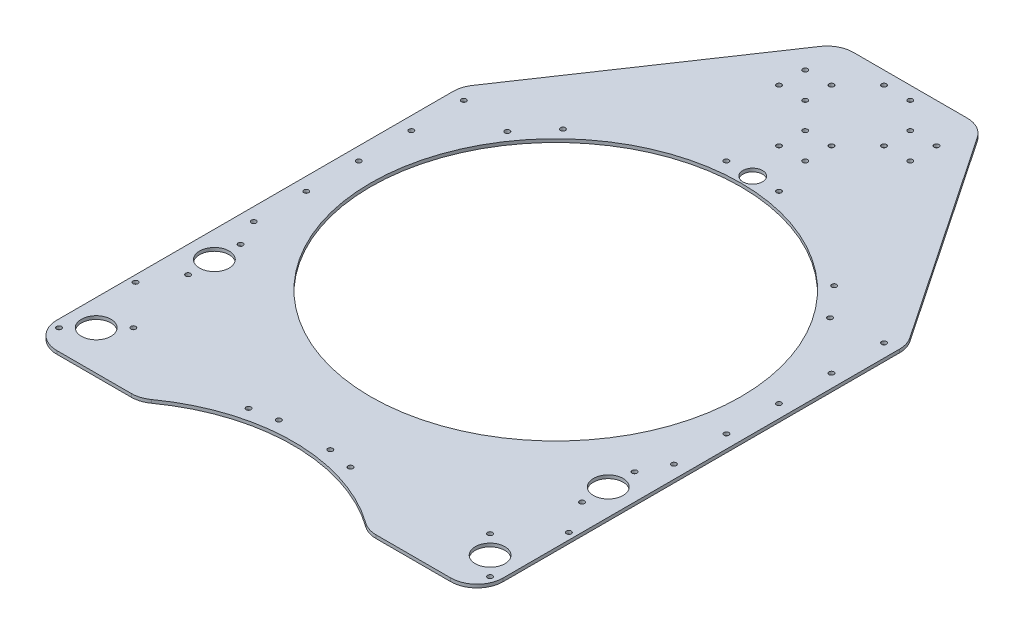
SolidWorks part; units mm, degrees
material "Thornel Mat VMA"
ref_plane "Front Plane" through (0, 0, 0) normal (0, 0, 1) x (1, 0, 0)
ref_plane "Top Plane" through (0, 0, 0) normal (0, 1, 0) x (1, 0, 0)
ref_plane "Right Plane" through (0, 0, 0) normal (1, 0, 0) x (0, 0, -1)
sketch "Sketch1" plane through (0, 0, 0) normal (0, 1, 0) x (1, 0, 0)
  line L1 (-215.9, 342.9) -> (215.9, 342.9)
  line L2 (-215.9, 342.9) -> (-215.9, -342.9)
  line L3 (-215.9, -342.9) -> (215.9, -342.9)
  line L4 (215.9, 342.9) -> (215.9, -342.9)
  line L5 (-215.9, 342.9) -> (215.9, -342.9) construction
  line L6 (-215.9, -342.9) -> (215.9, 342.9) construction
  point P0 (0, 0)
  dimension "D1" = 431.8
  dimension "D2" = 685.8
extrude "Boss-Extrude1" add sketch "Sketch1" along normal blind 3.175
sketch "Sketch2" plane through (0, 3.175, 0) normal (0, 1, 0) x (1, 0, 0)
  line L0 (0, -342.9) -> (0, 342.9) construction
  line L1 (-215.9, -342.9) -> (215.9, -342.9) construction
  line L2 (215.9, 342.9) -> (-215.9, 342.9) construction
  line L3 (-215.9, 342.9) -> (-215.9, -342.9) construction
  line L4 (-208.4605, -322.7605) -> (-190.5, -304.8) construction
  line L5 (-193.1461, -304.8) -> (-215.9, -304.8) construction
  circle A0 centre (-190.5, -304.8) radius 14.3129
  circle A1 centre (-190.5, -190.5) radius 14.3129
  circle A3 centre (190.5, -190.5) radius 14.3129
  circle A4 centre (190.5, -190.5) radius 25.4 construction
  circle A5 centre (-190.5, -190.5) radius 25.4 construction
  circle A6 centre (190.5, -215.9) radius 2.3813
  circle A7 centre (190.5, -165.1) radius 2.3813
  circle A8 centre (-190.5, -215.9) radius 2.3813
  circle A9 centre (-190.5, -165.1) radius 2.3813
  circle A10 centre (-190.5, -304.8) radius 25.4 construction
  circle A11 centre (-208.4605, -322.7605) radius 2.3813
  circle A15 centre (-172.5395, -286.8395) radius 2.3813
  circle A16 centre (172.5395, -286.8395) radius 2.3813
  circle A17 centre (208.4605, -322.7605) radius 2.3813
  circle A18 centre (190.5, -304.8) radius 14.3129
  point P33 (-190.5, -304.8)
  point P34 (-190.5, -304.8)
  dimension "D1" = 28.6258
  dimension "D2" = 28.6258
  dimension "D6" = 50.8
  dimension "D7" = 50.8
  dimension "D8" = 4.7625
  dimension "D9" = 4.7625
  dimension "D10" = 4.7625
  dimension "D11" = 4.7625
  dimension "D12" = 50.8
  dimension "D13" = 4.7625
  dimension "D3" = 38.1
  dimension "D4" = 114.3
  dimension "D5" = 25.4
  dimension "D15" = 45
  dimension "D14" = 2
extrude "Cut-Extrude1" cut sketch "Sketch2" against normal through all
sketch "Sketch3" plane through (0, 0, 0) normal (0, -1, 0) x (-1, 0, 0)
  line L1 (29.8706, 270.2084) -> (-24.7394, 270.2084)
  line L2 (29.8706, 270.2084) -> (29.8706, 216.2334)
  line L3 (29.8706, 216.2334) -> (-24.7394, 216.2334)
  line L4 (-24.7394, 270.2084) -> (-24.7394, 216.2334)
  line L5 (29.8706, 270.2084) -> (-24.7394, 216.2334) construction
  line L6 (29.8706, 216.2334) -> (-24.7394, 270.2084) construction
  point P0 (2.5656, 243.2209)
  dimension "D1" = 53.975
  dimension "D2" = 54.61
extrude "Boss-Extrude2" [suppressed] add sketch "Sketch3" along normal blind 203.2
fillet "Fillet1" [suppressed] radius 20.32
sketch "Sketch4" [suppressed] plane through (0, -203.2, 0) normal (0, -1, 0) x (-1, 0, 0)
  line L0 (-24.7394, 216.2334) -> (29.8706, 216.2334) construction
  line L1 (26.6956, 267.0334) -> (-21.5644, 267.0334)
  line L2 (26.6956, 267.0334) -> (26.6956, 219.4084)
  line L3 (26.6956, 219.4084) -> (-21.5644, 219.4084)
  line L4 (-21.5644, 267.0334) -> (-21.5644, 219.4084)
  line L5 (26.6956, 267.0334) -> (-21.5644, 219.4084) construction
  line L6 (26.6956, 219.4084) -> (-21.5644, 267.0334) construction
  line L7 (29.8706, 270.2084) -> (-24.7394, 270.2084) construction
  line L8 (29.8706, 216.2334) -> (29.8706, 270.2084) construction
  line L9 (-24.7394, 270.2084) -> (-24.7394, 216.2334) construction
  point P0 (2.5656, 243.2209)
  dimension "D1" = 3.175
  dimension "D2" = 3.175
  dimension "D3" = 3.175
  dimension "D4" = 3.175
extrude "Cut-Extrude2" [suppressed] cut sketch "Sketch4" against normal blind 203.2
sketch "Sketch5" [suppressed] plane through (-29.8706, 0, 0) normal (-1, 0, 0) x (0, 0, 1)
  line L0 (-216.2334, -203.2) -> (-216.2334, 0) construction
  line L1 (-216.2334, -203.2) -> (-270.2084, -203.2) construction
  circle A0 centre (-243.2209, -184.15) radius 14.2875
  dimension "D1" = 28.575
  dimension "D2" = 26.9875
  dimension "D3" = 19.05
extrude "Cut-Extrude3" [suppressed] cut sketch "Sketch5" against normal blind 203.2
sketch "Sketch6" plane through (0, 3.175, 0) normal (0, 1, 0) x (1, 0, 0)
  circle A0 centre (0, -50.8) radius 179.07
  dimension "D1" = 358.14
  dimension "D2" = 50.8
extrude "Cut-Extrude4" cut sketch "Sketch6" against normal through all
sketch "Sketch8" plane through (0, 3.175, 0) normal (0, 1, 0) x (1, 0, 0)
  circle A0 centre (0, 139.7) radius 9.525
  circle A2 centre (0, 139.7) radius 25.4 construction
  circle A3 centre (25.4, 139.7) radius 2.3813
  circle A4 centre (-25.4, 139.7) radius 2.3813
  dimension "D1" = 19.05
  dimension "D3" = 50.8
  dimension "D4" = 4.7625
  dimension "D5" = 4.7625
  dimension "D2" = 139.7
extrude "Cut-Extrude6" cut sketch "Sketch8" against normal through all
fillet "Fillet2" radius 25.4 2 edges at (215.9, 1.5875, 342.9) (-215.9, 1.5875, 342.9)
sketch "Sketch10" plane through (0, 3.175, 0) normal (0, 1, 0) x (1, 0, 0)
  line L0 (-215.9, 342.9) -> (-215.9, -317.5) construction
  line L1 (215.9, -317.5) -> (215.9, 342.9) construction
  circle A0 centre (-190.5, 215.9) radius 14.3129
  circle A1 centre (190.5, 215.9) radius 14.3129
  circle A2 centre (-190.5, 215.9) radius 25.4 construction
  circle A3 centre (190.5, 215.9) radius 25.4 construction
  circle A4 centre (190.5, 190.5) radius 2.3813
  circle A5 centre (190.5, 241.3) radius 2.3813
  circle A6 centre (-190.5, 190.5) radius 2.3813
  circle A7 centre (-190.5, 241.3) radius 2.3813
  circle A8 centre (190.5, -190.5) radius 14.3129 construction
  circle A9 centre (-190.5, -190.5) radius 14.3129 construction
  dimension "D1" = 28.6258
  dimension "D2" = 50.8
  dimension "D3" = 28.6258
  dimension "D4" = 50.8
  dimension "D5" = 4.7625
  dimension "D6" = 4.7625
  dimension "D7" = 4.7625
  dimension "D8" = 4.7625
  dimension "D9" = 25.4
  dimension "D10" = 25.4
  dimension "D11" = 406.4
  dimension "D12" = 406.4
extrude "Cut-Extrude8" [suppressed] cut sketch "Sketch10" against normal through all
sketch "Sketch11" plane through (0, 3.175, 0) normal (0, 1, 0) x (1, 0, 0)
  line L0 (0, -50.8) -> (156.0485, 58.4663) construction
  line L6 (0, 0) -> (0, 139.7) construction
  circle A0 centre (0, -50.8) radius 179.07
  circle A1 centre (0, -50.8) radius 179.07 construction
  circle A2 centre (0, -50.8) radius 184.15
  circle A3 centre (0, -50.8) radius 215.9
  circle A4 centre (156.0485, 58.4663) radius 2.3813
  circle A5 centre (131.1838, 87.3342) radius 2.3813
  circle A6 centre (0, -50.8) radius 190.5 construction
  circle A7 centre (-131.1838, 87.3342) radius 2.3813
  circle A8 centre (-156.0485, 58.4663) radius 2.3813
  dimension "D1" = 368.3
  dimension "D6" = 431.8
  dimension "D7" = 381
  dimension "D9" = 4.7625
  dimension "D10" = 4.7625
  dimension "D2" = 55
  dimension "D8" = 38.1
extrude "Cut-Extrude9" cut sketch "Sketch11" against normal through all contours A4 | A5 | A7 | A8 region at (156.0485, 3.175, -58.4663) region at (131.1838, 3.175, -87.3342) region at (-131.1838, 3.175, -87.3342) region at (-156.0485, 3.175, -58.4663)
sketch "Sketch13" plane through (0, 3.175, 0) normal (0, 1, 0) x (1, 0, 0)
  line L0 (-215.9, 342.9) -> (-215.9, -317.5) construction
  line L1 (215.9, 342.9) -> (-215.9, 342.9) construction
  line L2 (0, -342.9) -> (0, 342.9) construction
  line L3 (-190.5, -342.9) -> (190.5, -342.9) construction
  circle A0 centre (-203.2, 317.5) radius 2.3813
  circle A1 centre (-203.2, 266.7) radius 2.3813
  circle A2 centre (-203.2, 215.9) radius 2.3813
  circle A3 centre (-203.2, 165.1) radius 2.3813
  circle A4 centre (-203.2, 114.3) radius 2.3813
  circle A5 centre (-203.2, 63.5) radius 2.3813
  circle A6 centre (-203.2, 12.7) radius 2.3813
  circle A7 centre (-203.2, -38.1) radius 2.3813
  circle A8 centre (-203.2, -88.9) radius 2.3813
  circle A9 centre (-203.2, -139.7) radius 2.3813
  circle A10 centre (203.2, -139.7) radius 2.3813
  circle A11 centre (203.2, 12.7) radius 2.3813
  circle A12 centre (203.2, 63.5) radius 2.3813
  circle A13 centre (203.2, 114.3) radius 2.3813
  circle A14 centre (203.2, 165.1) radius 2.3813
  circle A15 centre (203.2, 266.7) radius 2.3813
  circle A16 centre (203.2, 317.5) radius 2.3813
  circle A17 centre (-25.4, -330.2) radius 2.4664
  circle A20 centre (-50.8, -330.2) radius 2.3078
  circle A21 centre (50.8, -330.2) radius 2.3078
  circle A22 centre (25.4, -330.2) radius 2.4664
  circle A23 centre (203.2, -88.9) radius 2.3813
  circle A24 centre (203.2, -38.1) radius 2.3813
  circle A25 centre (203.2, 215.9) radius 2.3813
  dimension "D1" = 4.7625
  dimension "D2" = 12.7
  dimension "D3" = 25.4
  dimension "D5" = 25.4
  dimension "D6" = 50.8
  dimension "D7" = 12.7
  dimension "D8" = 12.7
  dimension "D4" = 10
extrude "Cut-Extrude10" cut sketch "Sketch13" against normal through all
sketch "Sketch14" plane through (0, 3.175, 0) normal (0, 1, 0) x (1, 0, 0)
  line L0 (215.9, -317.5) -> (215.9, 342.9) construction
  line L1 (0, -342.9) -> (0, -229.87) construction
  line L2 (-190.5, -342.9) -> (190.5, -342.9) construction
  circle A0 centre (209.55, -247.65) radius 2.3813
  circle A2 centre (0, -50.8) radius 179.07 construction
  circle A3 centre (-209.55, -247.65) radius 2.3813
  circle A4 centre (190.5, -304.8) radius 14.3129 construction
  dimension "D1" = 57.15
  dimension "D3" = 4.7625
  dimension "D2" = 6.35
extrude "Cut-Extrude11" cut sketch "Sketch14" against normal through all
sketch "Sketch16" plane through (0, 3.175, 0) normal (0, 1, 0) x (1, 0, 0)
  line L0 (215.9, -317.5) -> (215.9, 342.9) construction
  line L1 (-215.9, 342.9) -> (215.9, 342.9)
  line L2 (-215.9, 342.9) -> (-215.9, 292.1)
  line L3 (-215.9, 292.1) -> (215.9, 292.1)
  line L4 (215.9, 342.9) -> (215.9, 292.1)
  dimension "D1" = 50.8
extrude "Cut-Extrude13" cut sketch "Sketch16" against normal through all
sketch "Sketch17" plane through (0, 0, 0) normal (0, -1, 0) x (-1, 0, 0)
  line L0 (0, -482.6) -> (0, 3.1553) construction
  line L1 (0, -482.6) -> (24.8652, -293.7298) construction
  line L2 (0, -482.6) -> (49.305, -298.5911) construction
  circle A0 centre (0, -482.6) radius 177.8
  circle A1 centre (0, -482.6) radius 190.5 construction
  circle A2 centre (24.8652, -293.7298) radius 2.3813
  circle A3 centre (49.305, -298.5911) radius 2.3813
  circle A4 centre (-24.8652, -293.7298) radius 2.3813
  circle A5 centre (-49.305, -298.5911) radius 2.3813
  dimension "D1" = 355.6
  dimension "D3" = 381
  dimension "D6" = 4.7625
  dimension "D7" = 4.7625
  dimension "D2" = 482.6
  dimension "D4" = 7.5
  dimension "D5" = 15
extrude "Cut-Extrude14" cut sketch "Sketch17" against normal through all
fillet "Fillet3" radius 25.4 2 edges at (109.9852, 1.5875, 342.9) (-109.9852, 1.5875, 342.9)
sketch "Sketch18" plane through (0, 3.175, 0) normal (0, 1, 0) x (1, 0, 0)
  line L0 (-215.9, 292.1) -> (215.9, 292.1) construction
  line L1 (25.4, 215.9) -> (-25.4, 215.9) construction
  line L2 (25.4, 215.9) -> (25.4, 266.7) construction
  line L3 (25.4, 266.7) -> (-25.4, 266.7) construction
  line L4 (-25.4, 215.9) -> (-25.4, 266.7) construction
  line L5 (25.4, 215.9) -> (-25.4, 266.7) construction
  line L6 (25.4, 266.7) -> (-25.4, 215.9) construction
  line L8 (25.4, 215.9) -> (76.2, 215.9) construction
  line L9 (25.4, 215.9) -> (25.4, 266.7) construction
  line L10 (25.4, 266.7) -> (76.2, 266.7) construction
  line L11 (76.2, 215.9) -> (76.2, 266.7) construction
  circle A0 centre (38.1, 228.6) radius 2.3812
  circle A1 centre (63.5, 228.6) radius 2.3813
  circle A2 centre (63.5, 254) radius 2.3813
  circle A3 centre (38.1, 254) radius 2.3813
  circle A4 centre (-12.7, 177.8) radius 2.3813
  circle A5 centre (-12.7, 203.2) radius 2.3813
  circle A6 centre (12.7, 177.8) radius 2.3813
  circle A7 centre (12.7, 203.2) radius 2.3812
  circle A8 centre (-63.5, 254) radius 2.3812
  circle A9 centre (-38.1, 254) radius 2.3813
  circle A10 centre (-63.5, 228.6) radius 2.3813
  circle A11 centre (-38.1, 228.6) radius 2.3813
  circle A12 centre (12.7, 304.8) radius 2.3812
  circle A13 centre (12.7, 279.4) radius 2.3812
  circle A14 centre (-12.7, 304.8) radius 2.3813
  circle A15 centre (-12.7, 279.4) radius 2.3812
  point P0 (0, 241.3)
  point P45 (0, 241.3)
  dimension "D5" = 4.7625
  dimension "D1" = 50.8
  dimension "D2" = 50.8
  dimension "D3" = 50.8
  dimension "D4" = 12.7
  dimension "D6" = 25.4
  dimension "D9" = 50.8
  dimension "D10" = 4
  dimension "D7" = 2
  dimension "D8" = 2
extrude "Cut-Extrude15" cut sketch "Sketch18" against normal through all
chamfer "Chamfer1" distance 147.32 angle 56 1 edges at (215.9, 1.5875, -292.1) first distance on face at (0, 1.5875, -292.1)
chamfer "Chamfer2" distance 147.32 angle 56 1 edges at (-215.9, 1.5875, -292.1) first distance on face at (-73.66, 1.5875, -292.1)
fillet "Fillet4" radius 25.4 4 edges at (68.58, 1.5875, -292.1) (-68.58, 1.5875, -292.1) (-215.9, 1.5875, -73.6891) (215.9, 1.5875, -73.6891)
